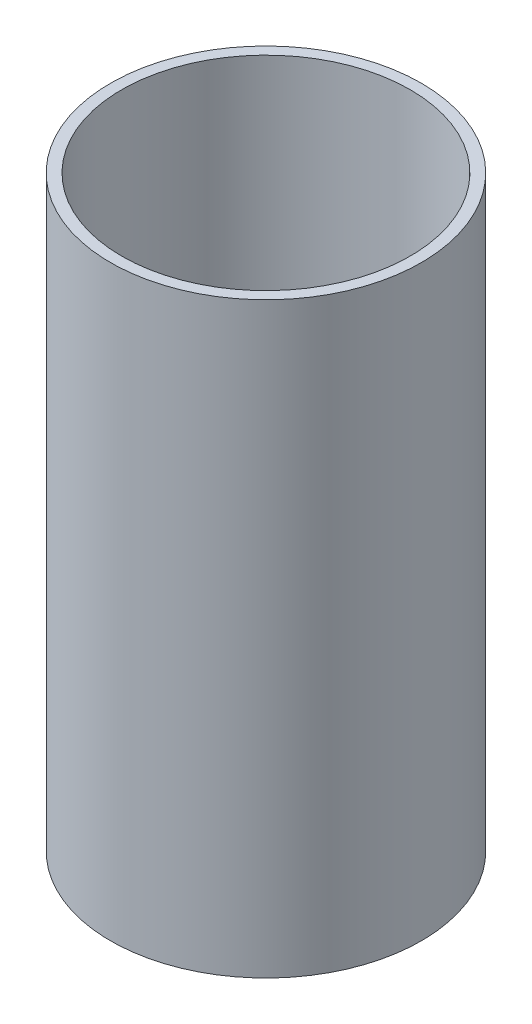
SolidWorks part; units mm, degrees
material "6063-T6"
ref_plane "Front Plane" through (0, 0, 0) normal (0, 0, 1) x (1, 0, 0)
ref_plane "Top Plane" through (0, 0, 0) normal (0, 1, 0) x (1, 0, 0)
ref_plane "Right Plane" through (0, 0, 0) normal (1, 0, 0) x (0, 0, -1)
sketch "Sketch1" plane through (0, 0, 0) normal (0, 1, 0) x (1, 0, 0)
  circle A0 centre (0, 0) radius 41.25
  circle A1 centre (0, 0) radius 44.45
  dimension "D1" = 88.9
  dimension "D2" = 3.2
extrude "Boss-Extrude1" add sketch "Sketch1" along normal blind 168
